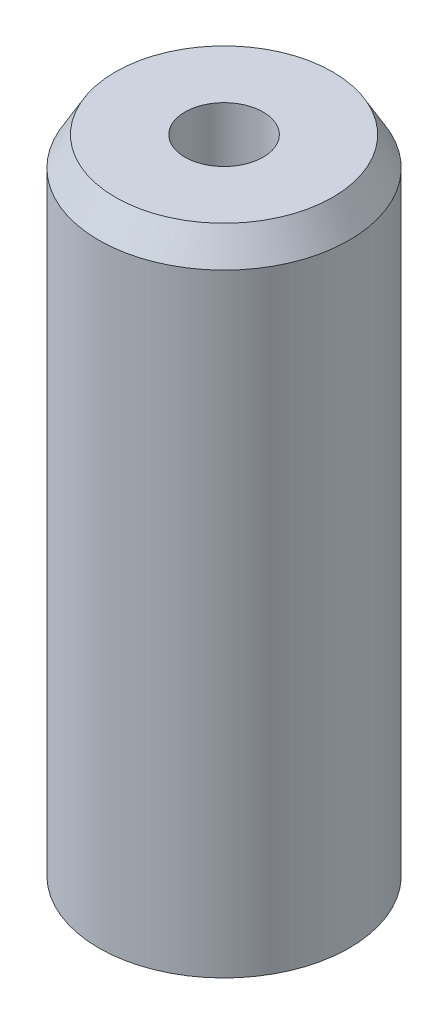
SolidWorks part; units mm, degrees
ref_plane "Front Plane" through (0, 0, 0) normal (0, 0, 1) x (1, 0, 0)
ref_plane "Top Plane" through (0, 0, 0) normal (0, 1, 0) x (1, 0, 0)
ref_plane "Right Plane" through (0, 0, 0) normal (1, 0, 0) x (0, 0, -1)
sketch "Sketch1" plane through (0, 0, 0) normal (0, 1, 0) x (1, 0, 0)
  circle A0 centre (0, 0) radius 12.5
  dimension "SHAFT_OD" = 25
extrude "Boss-Extrude1" add sketch "Sketch1" along normal blind 65.6975
sketch "Sketch2" plane through (0, 0, 0) normal (0, 1, 0) x (1, 0, 0)
  circle A0 centre (0, 0) radius 3.9052
  dimension "BORE_D" = 7.8105
extrude "Cut-Extrude1" cut sketch "Sketch2" along normal through all
chamfer "Chamfer1" distance 2.8762 angle 30 2 edges at (0, 65.6975, 12.5) (0, 0, 12.5) first distance on face at (0, 65.6975, 12.5) first distance on face at (0, 0, 3.9052)
